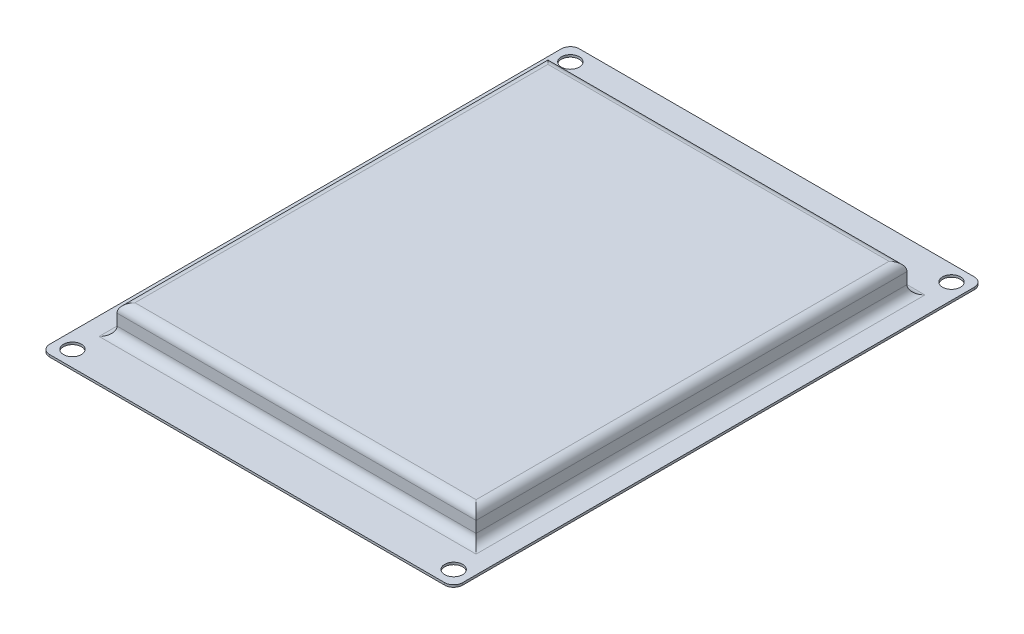
SolidWorks part; units mm, degrees
material "Acrylic (Medium-high impact)"
ref_plane "Front Plane" through (0, 0, 0) normal (0, 0, 1) x (1, 0, 0)
ref_plane "Top Plane" through (0, 0, 0) normal (0, 1, 0) x (1, 0, 0)
ref_plane "Right Plane" through (0, 0, 0) normal (1, 0, 0) x (0, 0, -1)
sketch "Sketch1" plane through (0, 0, 0) normal (0, 1, 0) x (1, 0, 0)
  line L1 (25, -31.5) -> (-25, -31.5)
  line L2 (25, -31.5) -> (25, 31.5)
  line L3 (25, 31.5) -> (-25, 31.5)
  line L4 (-25, -31.5) -> (-25, 31.5)
  line L5 (25, -31.5) -> (-25, 31.5) construction
  line L6 (25, 31.5) -> (-25, -31.5) construction
  line L7 (23, -29.5) -> (-23, -29.5)
  line L8 (23, -29.5) -> (23, 29.5)
  line L9 (23, 29.5) -> (-23, 29.5)
  line L10 (-23, -29.5) -> (-23, 29.5)
  line L11 (23, -29.5) -> (-23, 29.5) construction
  line L12 (23, 29.5) -> (-23, -29.5) construction
  point P0 (0, 0)
  point P6 (0, 0)
  dimension "D1" = 50
  dimension "D2" = 63
  dimension "D3" = 2
  dimension "D4" = 2
sketch "Sketch3" plane through (0, 0, 0) normal (0, 1, 0) x (1, 0, 0)
  line L0 (0, 29.5) -> (0, -29.5) construction
  line L1 (-18, 29.5) -> (18, 29.5)
  line L2 (23, 24.5) -> (23, -24.5)
  line L4 (18, -29.5) -> (-18, -29.5)
  line L5 (23, 0) -> (-23, 0) construction
  line L6 (-23, -24.5) -> (-23, 24.5)
  line L9 (-23, 29.5) -> (-19.4645, 25.9645) construction
  line L11 (-23, 29.5) -> (-23, 24.5)
  line L12 (-18, 29.5) -> (-23, 29.5)
  line L13 (-23, 24.5) -> (-23, 29.5)
  line L14 (-23, 29.5) -> (-18, 29.5)
  line L15 (-23, 29.5) -> (-23, 24.5)
  line L16 (-18, 29.5) -> (-23, 29.5)
  line L17 (-23, 24.5) -> (-23, 29.5)
  line L18 (-23, 29.5) -> (-18, 29.5)
  line L19 (-23, 29.5) -> (-23, 24.5)
  line L20 (-18, 29.5) -> (-23, 29.5)
  line L21 (-23, 24.5) -> (-23, 29.5)
  line L22 (-23, 29.5) -> (-18, 29.5)
  line L23 (-23, 29.5) -> (-23, 24.5)
  line L24 (-18, 29.5) -> (-23, 29.5)
  line L25 (23, 29.5) -> (19.4645, 25.9645) construction
  line L26 (18, 29.5) -> (23, 29.5)
  line L27 (23, 29.5) -> (23, 24.5)
  line L28 (23, 29.5) -> (18, 29.5)
  line L29 (23, 24.5) -> (23, 29.5)
  line L30 (18, 29.5) -> (23, 29.5)
  line L31 (23, 29.5) -> (23, 24.5)
  line L32 (23, 29.5) -> (18, 29.5)
  line L33 (23, 24.5) -> (23, 29.5)
  line L34 (18, 29.5) -> (23, 29.5)
  line L35 (23, 29.5) -> (23, 24.5)
  line L36 (23, 29.5) -> (18, 29.5)
  line L37 (23, 24.5) -> (23, 29.5)
  line L38 (18, 29.5) -> (23, 29.5)
  line L39 (23, 29.5) -> (23, 24.5)
  line L40 (23, 29.5) -> (18, 29.5)
  line L41 (23, 24.5) -> (23, 29.5)
  line L42 (23, -29.5) -> (19.4645, -25.9645)
  line L43 (-23, -29.5) -> (-19.4645, -25.9645)
  line L44 (23, -24.5) -> (23, -29.5)
  line L45 (23, -29.5) -> (18, -29.5)
  line L46 (23, -29.5) -> (23, -24.5)
  line L47 (18, -29.5) -> (23, -29.5)
  line L48 (23, -24.5) -> (23, -29.5)
  line L49 (23, -29.5) -> (18, -29.5)
  line L50 (23, -29.5) -> (23, -24.5)
  line L51 (18, -29.5) -> (23, -29.5)
  line L52 (23, -24.5) -> (23, -29.5)
  line L53 (23, -29.5) -> (18, -29.5)
  line L54 (23, -29.5) -> (23, -24.5)
  line L55 (18, -29.5) -> (23, -29.5)
  line L56 (23, -24.5) -> (23, -29.5)
  line L57 (23, -29.5) -> (18, -29.5)
  line L58 (23, -29.5) -> (23, -24.5)
  line L59 (18, -29.5) -> (23, -29.5)
  line L60 (-18, -29.5) -> (-23, -29.5)
  line L61 (-23, -29.5) -> (-23, -24.5)
  line L62 (-23, -29.5) -> (-18, -29.5)
  line L63 (-23, -24.5) -> (-23, -29.5)
  line L64 (-18, -29.5) -> (-23, -29.5)
  line L65 (-23, -29.5) -> (-23, -24.5)
  line L66 (-23, -29.5) -> (-18, -29.5)
  line L67 (-23, -24.5) -> (-23, -29.5)
  line L68 (-18, -29.5) -> (-23, -29.5)
  line L69 (-23, -29.5) -> (-23, -24.5)
  line L70 (-23, -29.5) -> (-18, -29.5)
  line L71 (-23, -24.5) -> (-23, -29.5)
  line L72 (-18, -29.5) -> (-23, -29.5)
  line L73 (-23, -29.5) -> (-23, -24.5)
  line L74 (-23, -29.5) -> (-18, -29.5)
  line L75 (-23, -24.5) -> (-23, -29.5)
  arc A0 (-23, 24.5) -> (-18, 29.5) centre (-23, 29.5) ccw
  circle A1 centre (-21.2322, 27.7322) radius 1
  circle A3 centre (21.2322, 27.7322) radius 1
  arc A4 (23, 24.5) -> (18, 29.5) centre (23, 29.5) cw
  arc A7 (23, -24.5) -> (18, -29.5) centre (23, -29.5) ccw
  circle A8 centre (21.2322, -27.7322) radius 1
  circle A9 centre (-21.2322, -27.7322) radius 1
  arc A10 (-23, -24.5) -> (-18, -29.5) centre (-23, -29.5) cw
  point P2 (0, 0)
  point P7 (0, 0)
  dimension "D2" = 2
  dimension "D1" = 5
  dimension "D3" = 46
  dimension "D4" = 59
extrude "Boss-Extrude1" add sketch "Sketch3" along normal blind 0.25 contours L6 A10 L4 A7 L2 A4 L1 A0 | L11 A0 L12 A1 | A4 L27 L26 A3 | A10 L43 A9 L60 | A10 L61 L43 A9 | A8 L42 L44 A7 | A8 L42 A7 L45 region at (-19.5145, 0, -26.0145) region at (0, 0, 0) region at (20.5, 0, -29.4293) region at (-21.7997, 0, 26.3212) region at (21.7997, 0, 26.3212) region at (-19.8212, 0, 28.2997) region at (19.8212, 0, 28.2997)
sketch "Sketch4" plane through (0, 0.25, 0) normal (0, 1, 0) x (1, 0, 0)
  line L1 (20, -24) -> (-20, -24)
  line L2 (20, -24) -> (20, 24)
  line L3 (20, 24) -> (-20, 24)
  line L4 (-20, -24) -> (-20, 24)
  line L5 (20, -24) -> (-20, 24) construction
  line L6 (20, 24) -> (-20, -24) construction
  point P0 (0, 0)
  dimension "D1" = 40
  dimension "D2" = 48
extrude "Boss-Extrude2" add sketch "Sketch4" along normal blind 3.25
shell "Shell4" thickness 0.5 removed face at (-21.2322, 0, 28.7322)
fillet "Fillet1" radius 1 8 edges at (0, 0.25, -24) (20, 0.25, 0) (0, 0, 23.5) (-20, 0.25, 0) (0, 0.25, 24) (19.5, 0, 0) (0, 0, -23.5) (-19.5, 0, 0)
fillet "Fillet2" radius 1 8 edges at (0, 3.5, -24) (20, 3.5, 0) (0, 3.5, 24) (-20, 3.5, 0) (0, 3, 23.5) (19.5, 3, 0) (0, 3, -23.5) (-19.5, 3, 0)
fillet "Fillet3" radius 1 4 edges at (-23, 0.125, 29.5) (23, 0.125, 29.5) (23, 0.125, -29.5) (-23, 0.125, -29.5)
